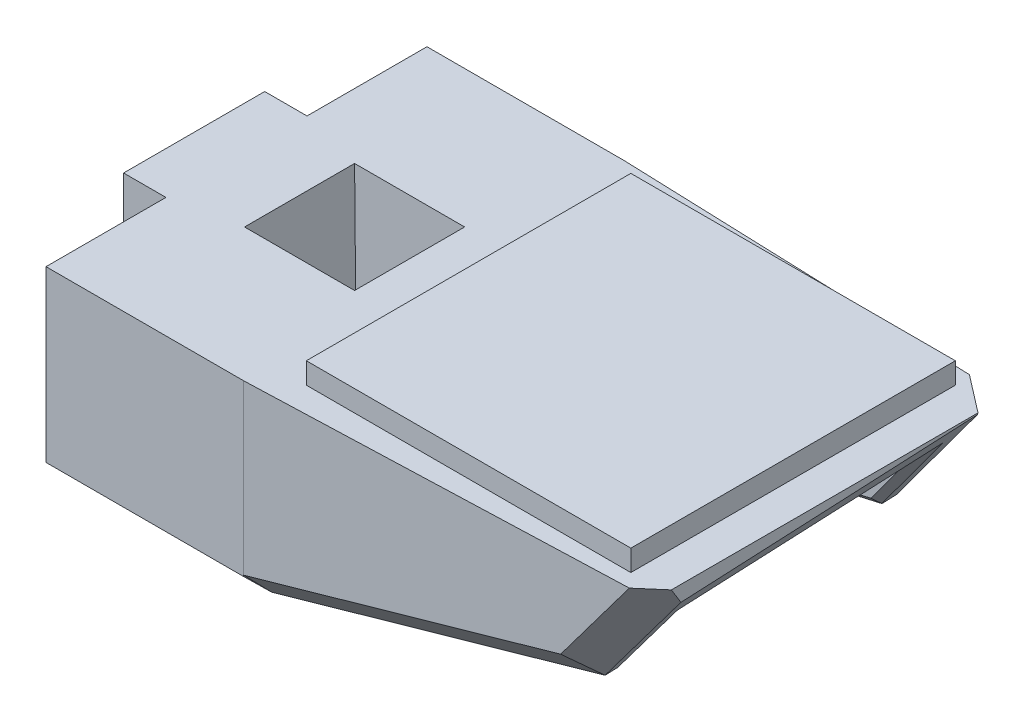
SolidWorks part; units mm, degrees
note: '?' marks a value the reader was unsure of.
ref_plane "Front Plane" through (0, 0, 0) normal (0, 0, 1) x (1, 0, 0)
ref_plane "Top Plane" through (0, 0, 0) normal (0, 1, 0) x (1, 0, 0)
ref_plane "Right Plane" through (0, 0, 0) normal (1, 0, 0) x (0, 0, -1)
sketch "Sketch2" plane through (0, 0, 0) normal (0, 1, 0) x (1, 0, 0)
  line L1 (14, 13.5) -> (-14, 13.5)
  line L2 (14, 13.5) -> (14, -13.5)
  line L3 (14, -13.5) -> (-14, -13.5)
  line L4 (-14, 13.5) -> (-14, -13.5)
  line L5 (14, 13.5) -> (-14, -13.5) construction
  line L6 (14, -13.5) -> (-14, 13.5) construction
  point P0 (0, 0)
  dimension "D1" = 28
  dimension "D2" = 27
extrude "Boss-Extrude1" add sketch "Sketch2" along normal blind 14
sketch "Sketch3" plane through (0, 0, 0) normal (0, -1, 0) x (1, 0, 0)
  line L1 (14, 13.5) -> (14, -13.5) construction
  line L2 (14, 12.5) -> (-14, 13.5)
  line L3 (-14, -13.5) -> (14, -12.5)
  line L4 (-14, 13.5) -> (14, 13.5)
  line L5 (14, 13.5) -> (14, 12.5)
  line L6 (-14, -13.5) -> (14, -13.5)
  line L7 (14, -13.5) -> (14, -12.5)
  point P5 (13, 0)
  dimension "D1" = 25
extrude "Cut-Extrude1" cut sketch "Sketch3" against normal through all both and the other way through all
sketch "Sketch4" plane through (0.4637, 0, 12.9834) normal (0.0357, 0, 0.9994) x (0.9994, 0, -0.0357)
  line L2 (-14.4729, 0) -> (13.5449, 0) construction
  line L3 (4.3935, 0) -> (13.5449, 0)
  line L6 (14.4372, 14) -> (14.4372, 0) construction
  line L7 (14.4372, 3.2009) -> (14.4372, 0)
  line L8 (14.4372, 0) -> (13.5449, 0)
  line L9 (-14.4729, 0) -> (8.4231, 5.9157)
  line L10 (8.4231, 5.9157) -> (14.4372, 14)
  line L11 (-14.4729, 0) -> (4.3935, 0)
  line L12 (14.4372, 3.2009) -> (14.4372, 14)
extrude "Cut-Extrude2" cut sketch "Sketch4" against normal through all both
sketch "Sketch7" plane through (-0.9051, 3.5054, 0.0323) normal (0.25, -0.9682, -0.0089) x (0.9682, 0.25, 0.0023)
  line L0 (-11.5243, 10) -> (-11.5243, -10)
  line L1 (15.0264, 9) -> (15.0264, -9)
  line L2 (-11.5243, 10) -> (15.0264, 9)
  line L3 (15.0264, -9) -> (-11.5243, -10)
  line L4 (-13.5243, -13.5017) -> (-13.5243, 13.4994) construction
  point P4 (15.0264, 0)
  point P5 (-11.5243, 0)
  dimension "D1" = 20
  dimension "D2" = 18
  dimension "D3" = 2
  dimension "D4" = 2
extrude "Cut-Extrude5" cut sketch "Sketch7" against normal blind 5
chamfer "Chamfer9" distance 2 angle 45 4 edges at (10.9872, 9.9578, -12.6076) (-3.0128, 3.0823, -13.1076) (11.4407, 9.3581, 12.5914)
chamfer "Chamfer10" distance 0.5 angle 45 6 edges at (10.6928, 8.5173, 9.174) (12.56, 11.4607, 0.1057) (10.2972, 8.8591, -9.0265) (-1.6524, 3.224, 9.6252) (-12.0635, 0.6245, 0.0058) (-1.9811, 3.3162, -9.5776)
sketch "Sketch8" plane through (0, 14, 0) normal (0, 1, 0) x (1, 0, 0)
  line L0 (-11.5, 11.45) -> (-11.5, -11.55)
  line L1 (-11.5, 11.45) -> (11.5, 11.45)
  line L3 (-11.5, -11.55) -> (11.5, -11.55)
  line L5 (11.5, 11.45) -> (11.5, -11.55)
  point P2 (-11.5, -0.05)
  dimension "D1" = 0.05
  dimension "D2" = 23
  dimension "D3" = 23
  dimension "D4" = 11.5
extrude "Boss-Extrude3" add sketch "Sketch8" along normal blind 1.5 separate body
sketch "Sketch9" plane through (-14, 0, 0) normal (-1, 0, 0) x (0, 0, 1)
  line L0 (13.5, 14) -> (13.5, 0)
  line L1 (13.5, 14) -> (-13.5, 14)
  line L7 (-13.5, 14) -> (-13.5, 2.3522) construction
  line L8 (13.5, 0) -> (-13.5, 0.249)
  line L9 (-13.5, 0.249) -> (-13.5, 14)
extrude "Boss-Extrude4" add sketch "Sketch9" along normal blind 14
chamfer "Chamfer11" distance 2 angle 45 2 edges at (-21, 0, 13.5) (-21, 0.249, -13.5)
sketch "Sketch11" plane through (0, 0.1245, 0.0011) normal (0, -1, -0.0092) x (1, 0, 0)
  line L0 (-14, -11.483) -> (-14, 11.4981) construction
  line L1 (-14, -5) -> (-25, -5)
  line L2 (-14, -5) -> (-14, 5)
  line L3 (-14, 5) -> (-25, 5)
  line L4 (-25, -5) -> (-25, 5)
  point P6 (-14, 0)
  dimension "D1" = 11
  dimension "D2" = 10
extrude "Boss-Extrude5" add sketch "Sketch11" along normal blind 2
sketch "Sketch12" plane through (0, -1.8754, -0.0173) normal (0, -1, -0.0092) x (1, 0, 0)
  line L1 (-15.6, 3.9) -> (-23.4, 3.9)
  line L2 (-15.6, 3.9) -> (-15.6, -3.9)
  line L3 (-15.6, -3.9) -> (-23.4, -3.9)
  line L4 (-23.4, 3.9) -> (-23.4, -3.9)
  line L5 (-15.6, 3.9) -> (-23.4, -3.9) construction
  line L6 (-15.6, -3.9) -> (-23.4, 3.9) construction
  line L7 (-14, 5) -> (-25, 5) construction
  line L8 (-25, 5) -> (-25, -5) construction
  point P0 (-19.5, 0)
  point P9 (-19.5, 5)
  point P10 (-25, 0)
  dimension "D1" = 7.8
  dimension "D2" = 7.8
extrude "Cut-Extrude6" cut sketch "Sketch12" against normal through all both and the other way through all
sketch "Sketch13" plane through (-28, 0, 0) normal (-1, 0, 0) x (0, 0, 1)
  line L0 (5.0009, 0.0784) -> (-4.9986, 0.1706) construction
  line L2 (4.9998, 0.0784) -> (4.9998, 14)
  line L3 (4.9998, 14) -> (-4.9998, 14)
  line L4 (-4.9998, 0.1706) -> (-4.9998, 14)
  line L5 (13.5, 14) -> (-13.5, 14) construction
  line L6 (-4.9998, 0.1706) -> (4.9998, 0.0784)
  line L7 (-11.4814, 0.2304) -> (11.5001, 0.0184) construction
  point P8 (0, 0.1245)
  dimension "D1" = 10
extrude "Boss-Extrude6" add sketch "Sketch13" along normal blind 3
ref_plane "Plane1" through (0, 35.887, 0.3309) normal (0, -1, -0.0092) x (-1, 0, 0)
ref_plane "Plane2" through (-19.5, 0, 0) normal (1, 0, 0) x (0, 0, -1)
sketch "Sketch14" plane through (0, -19.1106, -0.1762) normal (0, -1, -0.0092) x (1, 0, 0)
  line L1 (-20.7309, 0) -> (-18.2806, 0) construction
  line L2 (-20.7309, 0.65) -> (-20.7309, -0.65) construction
  line L3 (-39.6, 0) -> (-15.6, 0) construction
sketch "Sketch15" plane through (0, 90.8847, 0.8381) normal (0, 1, 0.0092) x (1, 0, 0)
  line L0 (-20.7309, 0) -> (-18.2806, 0) construction
  line L1 (-20.7309, 0) -> (-18.2806, 0)
ref_point "Point1"
ref_axis "Axis1" through (-19.5058, 90.8847, 0.8381) along (0, -1, -0.0092)?
ref_point "Point2"
chamfer "Chamfer13" distance 0.2 angle 45 4 edges at (-19.5, -1.9215, 4.9825) (-25, -1.8754, -0.0173) (-14, -1.8754, -0.0173) (-19.5, -1.8293, -5.0171)
chamfer "Chamfer14" distance 0.2 angle 45 4 edges at (-14, -0.8216, 4.9926) (-14, -0.7294, -5.0069) (-25, -0.7294, -5.0069) (-25, -0.8216, 4.9926)
